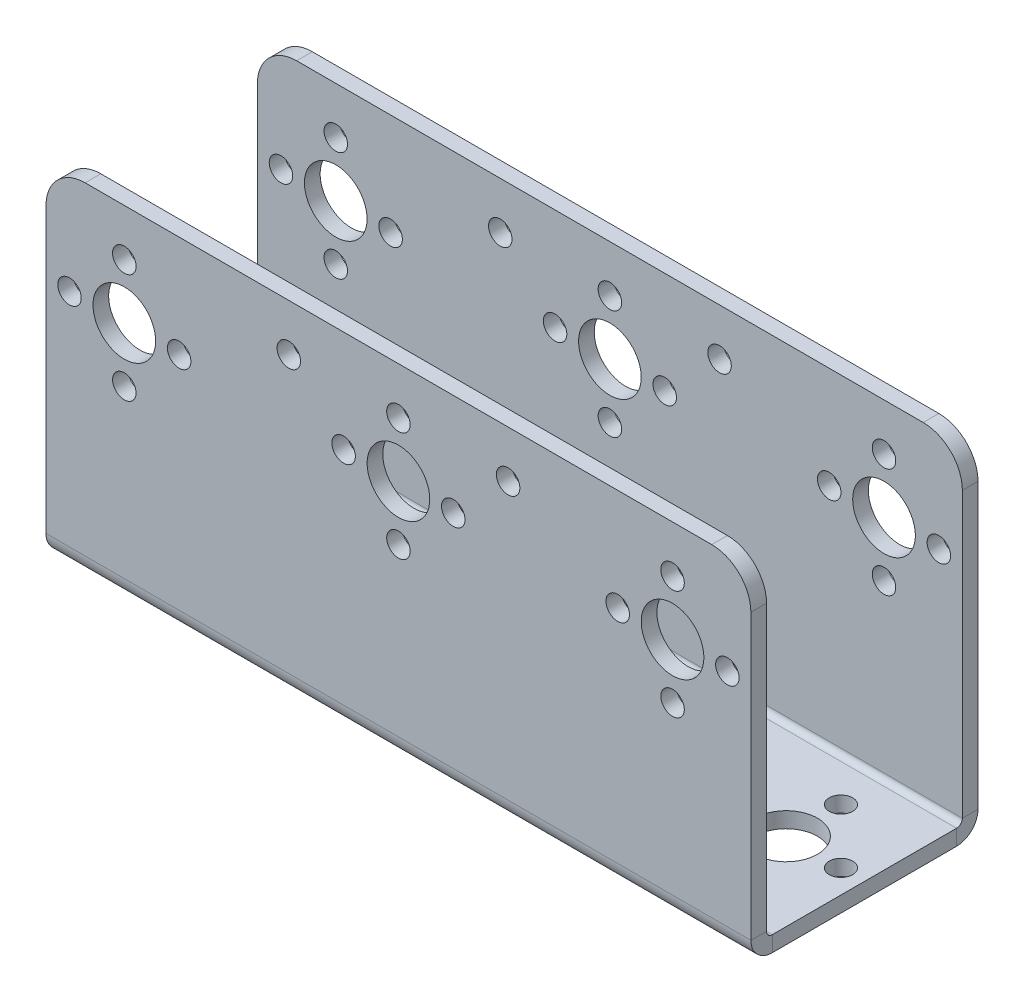
SolidWorks part; units mm, degrees
note: The reader was unsure of these and kept them because the rebuilt part matched: flange length of "边线-法兰1".
material "普通碳钢"
ref_plane "前视" through (0, 0, 0) normal (0, 0, 1) x (1, 0, 0)
ref_plane "上视" through (0, 0, 0) normal (0, 1, 0) x (1, 0, 0)
ref_plane "右视" through (0, 0, 0) normal (1, 0, 0) x (0, 0, -1)
sketch "草图1" plane through (0, 0, 0) normal (0, 1, 0) x (1, 0, 0)
  line L0 (0, -14.5) -> (90, -14.5) construction
  line L1 (0, 0) -> (90, 0)
  line L2 (0, 0) -> (0, -29)
  line L3 (0, -29) -> (90, -29)
  line L4 (90, 0) -> (90, -29)
  line L5 (10, -7.5) -> (10, -21.5) construction
  line L6 (45, -7.5) -> (45, -21.5) construction
  circle A0 centre (45, -14.5) radius 4
  circle A1 centre (10, -14.5) radius 4
  circle A2 centre (80, -14.5) radius 4
  circle A3 centre (10, -7.5) radius 1.5
  circle A4 centre (10, -21.5) radius 1.5
  circle A5 centre (17, -14.5) radius 1.5
  circle A6 centre (3, -14.5) radius 1.5
  circle A7 centre (10, -14.5) radius 7 construction
  circle A8 centre (45, -7.5) radius 1.5
  circle A9 centre (45, -21.5) radius 1.5
  circle A10 centre (52, -14.5) radius 1.5
  circle A11 centre (38, -14.5) radius 1.5
  circle A12 centre (45, -14.5) radius 7 construction
  circle A13 centre (87, -14.5) radius 1.5
  circle A14 centre (80, -21.5) radius 1.5
  circle A15 centre (73, -14.5) radius 1.5
  circle A16 centre (80, -7.5) radius 1.5
  dimension "D3" = 8
  dimension "D4" = 35
  dimension "D5" = 35
  dimension "D6" = 14
  dimension "D7" = 3
  dimension "D8" = 14
  dimension "D9" = 3
  dimension "D1" = 90
  dimension "D2" = 29
base flange "基体-法兰1" sketch "草图1" thickness 2 reverse thickness direction no parameters "D1"=0.7366
edge flange "边线-法兰1" sketch "草图10" flange profiles "草图10", "草图11" flange angle 90 flange length 44 flange position material inside bend radius 0.7366 thickness 2 relief rectangular parameters "D6"=0, "D8"=1
sketch "草图10" plane through (0, 0, 0) normal (0, 0, 1) x (1, 0, 0)
  line L2 (0, 0) -> (0, 42)
  line L3 (0, 42) -> (90, 42)
  line L4 (90, 42) -> (90, 0)
  line L6 (90, 0) -> (0, 0) construction
  line L7 (90, 0) -> (0, 0)
sketch "草图11" plane through (0, 0, 29) normal (0, 0, -1) x (-1, 0, 0)
  line L0 (0, 0) -> (-90, 0) construction
  line L1 (0, 0) -> (-90, 0)
  line L2 (0, 0) -> (0, 42)
  line L3 (0, 42) -> (-90, 42)
  line L4 (-90, 42) -> (-90, 0)
bend "边线折弯1" bend radius 0.7366 bend angle 90 parameters "D5"=1
bend "边线折弯2" bend radius 0.7366 bend angle 90 parameters "D5"=2
sketch "草图12" plane through (0, 0, 29) normal (0, 0, 1) x (1, 0, 0)
  line L0 (0, 29) -> (90, 29) construction
  line L1 (0, 0.7366) -> (0, 42) construction
  line L2 (90, 42) -> (90, 0.7366) construction
  line L3 (0, 42) -> (90, 42) construction
  line L4 (10, 36) -> (10, 22) construction
  line L5 (45, 36) -> (45, 22) construction
  line L6 (0, 36) -> (90, 36) construction
  circle A0 centre (45, 29) radius 4
  circle A1 centre (80, 29) radius 4
  circle A2 centre (10, 29) radius 4
  circle A3 centre (10, 36) radius 1.5
  circle A4 centre (10, 22) radius 1.5
  circle A5 centre (17, 29) radius 1.5
  circle A6 centre (3, 29) radius 1.5
  circle A7 centre (10, 29) radius 7 construction
  circle A8 centre (45, 36) radius 1.5
  circle A9 centre (45, 22) radius 1.5
  circle A10 centre (52, 29) radius 1.5
  circle A11 centre (38, 29) radius 1.5
  circle A12 centre (45, 29) radius 7 construction
  circle A13 centre (87, 29) radius 1.5
  circle A14 centre (80, 36) radius 1.5
  circle A15 centre (73, 29) radius 1.5
  circle A16 centre (80, 22) radius 1.5
  circle A17 centre (31, 36) radius 1.5
  circle A18 centre (59, 36) radius 1.5
  dimension "D2" = 8
  dimension "D3" = 35
  dimension "D4" = 35
  dimension "D5" = 3
  dimension "D6" = 14
  dimension "D7" = 14
  dimension "D8" = 3
  dimension "D9" = 3
  dimension "D10" = 28
  dimension "D1" = 13
  dimension "D11" = 6
extrude "切除-拉伸1" cut sketch "草图12" against normal blind 55 normal cut yes
fillet "圆角1" radius 5 4 edges at (90, 42, 1) (90, 42, 28) (0, 42, 1) (0, 42, 28)
sketch "折弯-线1" plane through (0, 0, 0) normal (0, 1, 0) x (1, 0, 0)
sketch "边界框1" plane through (0, 0, 0) normal (0, 1, 0) x (1, 0, 0)
sheet metal parameters "钣金4" thickness 2 parameters "D1"=0.7366
flat pattern "平板型式4" [suppressed]
sketch "折弯-线2" plane through (0, 0, 0) normal (0, 1, 0) x (1, 0, 0)
sketch "边界框2" [suppressed] plane through (0, 0, 0) normal (0, 1, 0) x (1, 0, 0)
sheet metal parameters "钣金5" thickness 2 parameters "D1"=0.7366
flat pattern "平板型式4" [suppressed]
sketch "折弯-线2" plane through (0, 0, 0) normal (0, 1, 0) x (1, 0, 0)
sketch "边界框2" [suppressed] plane through (0, 0, 0) normal (0, 1, 0) x (1, 0, 0)
bend of the flat pattern "展开-<边线折弯1>1"
bend of the flat pattern "展开-<边线折弯2>1"
sheet metal parameters "钣金6" thickness 2 parameters "D1"=0.7366
flat pattern "平板型式4"
sketch "折弯-线2" plane through (0, 0, 0) normal (0, 1, 0) x (1, 0, 0)
  line L0 (0, -27.6273) -> (90, -27.6273) construction
  line L1 (90, -1.3727) -> (0, -1.3727) construction
  line L2 (0, -27.6273) -> (90, -27.6273) construction
  line L3 (90, -1.3727) -> (0, -1.3727) construction
sketch3d "边界框2" [suppressed]
  line L0 (90, 41.2546, 0) -> (90, -70.2546, 0) construction
  line L1 (0, 41.2546, 0) -> (0, -70.2546, 0) construction
  line L2 (90, 41.2546, 0) -> (0, 41.2546, 0) construction
  line L3 (90, -70.2546, 0) -> (0, -70.2546, 0) construction
bend of the flat pattern "展开-<边线折弯1>1"
bend of the flat pattern "展开-<边线折弯2>1"
